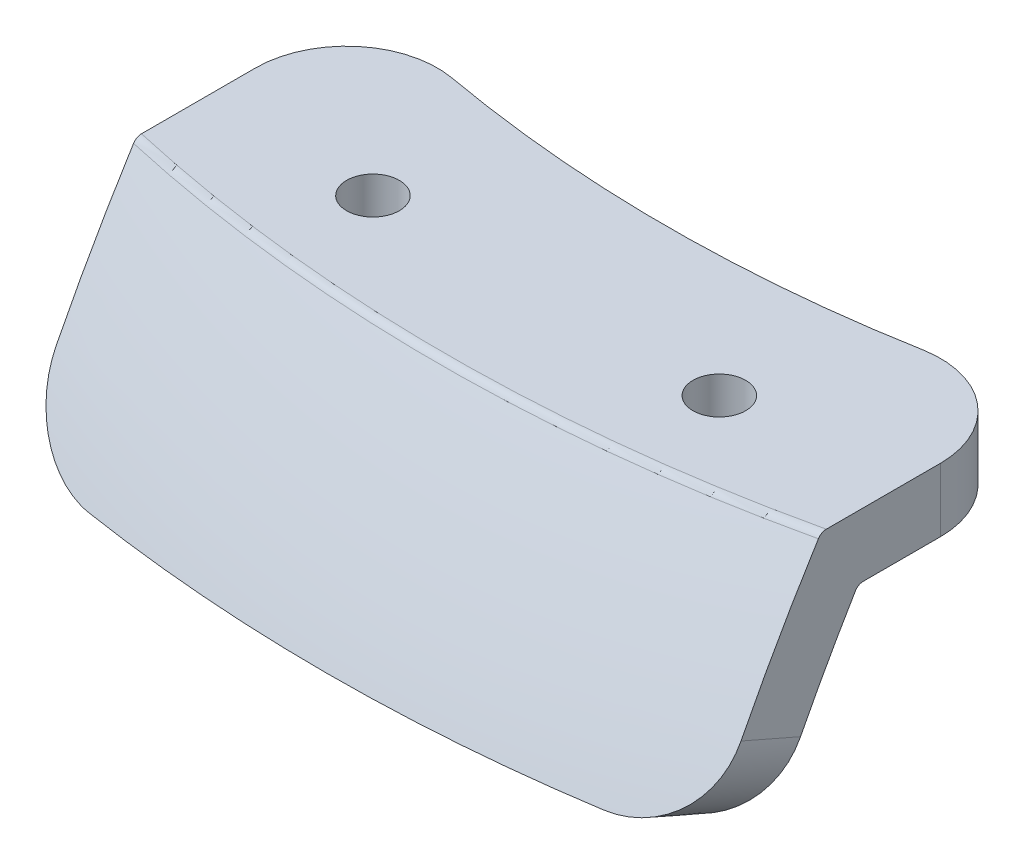
SolidWorks part; units mm, degrees
material "Polyether Polyol"
ref_plane "Front Plane" through (0, 0, 0) normal (0, 0, 1) x (1, 0, 0)
ref_plane "Top Plane" through (0, 0, 0) normal (0, 1, 0) x (1, 0, 0)
ref_plane "Right Plane" through (0, 0, 0) normal (1, 0, 0) x (0, 0, -1)
sketch "Sketch1" plane through (0, 0, 0) normal (1, 0, 0) x (0, 0, -1)
  line L0 (-182.9297, 172.8317) -> (-176.5279, 170.0001) construction
  line L1 (-170.3849, 196.7005) -> (-145.5262, 196.7005) construction
  line L9 (-145.5262, 196.7005) -> (-145.5262, 189.7005) construction
  line L10 (-145.5262, 189.7005) -> (-166.4259, 189.7005) construction
  line L11 (-182.9297, 172.8317) -> (-176.5279, 170.0001)
  line L12 (-170.3849, 196.7005) -> (-145.5262, 196.7005)
  line L13 (-145.5262, 196.7005) -> (-145.5262, 189.7005)
  line L14 (-145.5262, 189.7005) -> (-166.4259, 189.7005)
  line L15 (0, 0) -> (0, 91.9198) construction
  arc A5 (-166.4259, 189.7005) -> (-176.5279, 170.0001) centre (0, 91.9198) ccw construction
  arc A6 (-170.3849, 196.7005) -> (-182.9297, 172.8317) centre (0, 91.9198) ccw construction
  arc A7 (-166.4259, 189.7005) -> (-176.5279, 170.0001) centre (0, 91.9198) ccw
  arc A8 (-170.3849, 196.7005) -> (-182.9297, 172.8317) centre (0, 91.9198) ccw
revolve "Revolve1" add sketch "Sketch1" angle 30 mid plane about L15
sketch "Sketch2" plane through (0, 0, 0) normal (-1, 0, 0) x (0, 0, 1)
  line L0 (0, 91.9198) -> (171.9865, 179.5513) construction
  line L3 (0, -200000) -> (0, 218797.9879) construction
  arc A0 (176.5279, 170.0001) -> (166.4259, 189.7005) centre (0, 91.9198) ccw construction
  dimension "D1" = 63
ref_plane "Plane1" through (0, 72.9744, -37.1823) normal (0, -0.891, 0.454) x (0, 0.454, 0.891)
sketch "Sketch4" plane through (0, 72.9744, -37.1823) normal (0, -0.891, 0.454) x (0, 0.454, 0.891)
  line L0 (219.8801, 19.237) -> (239.1484, 20.9228) construction
  line L1 (219.7494, 20.7313) -> (239.0177, 22.4171)
  line L2 (219.7494, 20.7313) -> (219.8801, 19.237)
  line L3 (41.7307, 0) -> (234.7557, 0) construction
  line L4 (219.8801, 19.237) -> (239.1484, 20.9228)
  line L5 (239.0177, 22.4171) -> (239.1484, 20.9228)
  dimension "D1" = 3
  dimension "D2" = 5
revolve "Cut-Revolve1" cut sketch "Sketch4" angle 360 about L0
mirror "Mirror1" about plane through (0, 0, 0) normal (1, 0, 0) of "Cut-Revolve1"
sketch "Sketch5" plane through (0, 0, 0) normal (0, 1, 0) x (1, 0, 0)
  line L1 (37.665, -140.5675) -> (-37.665, -140.5675)
  line L2 (37.665, -140.5675) -> (37.665, -182.9297)
  line L3 (37.665, -182.9297) -> (-37.665, -182.9297)
  line L4 (-37.665, -140.5675) -> (-37.665, -182.9297)
  arc A0 (-47.3457, -176.6965) -> (47.3457, -176.6965) centre (0, 0) ccw construction
extrude "Cut-Extrude2" cut sketch "Sketch5" along normal through all flip side to cut
fillet "Fillet1" radius 10 4 edges at (-37.665, 193.2005, 140.5675) (37.665, 193.2005, 140.5675)
fillet "Fillet2" radius 1 2 edges at (0, 196.7005, 170.3849) (0, 189.7005, 166.4259)
sketch "Sketch6" plane through (0, 196.7005, 0) normal (0, 1, 0) x (1, 0, 0)
  circle A0 centre (19.05, -158.75) radius 2.9 construction
  circle A1 centre (-19.05, -158.75) radius 2.9 construction
  circle A2 centre (19.05, -158.75) radius 2.9
  circle A3 centre (-19.05, -158.75) radius 2.9
extrude "Cut-Extrude3" cut sketch "Sketch6" against normal through all
